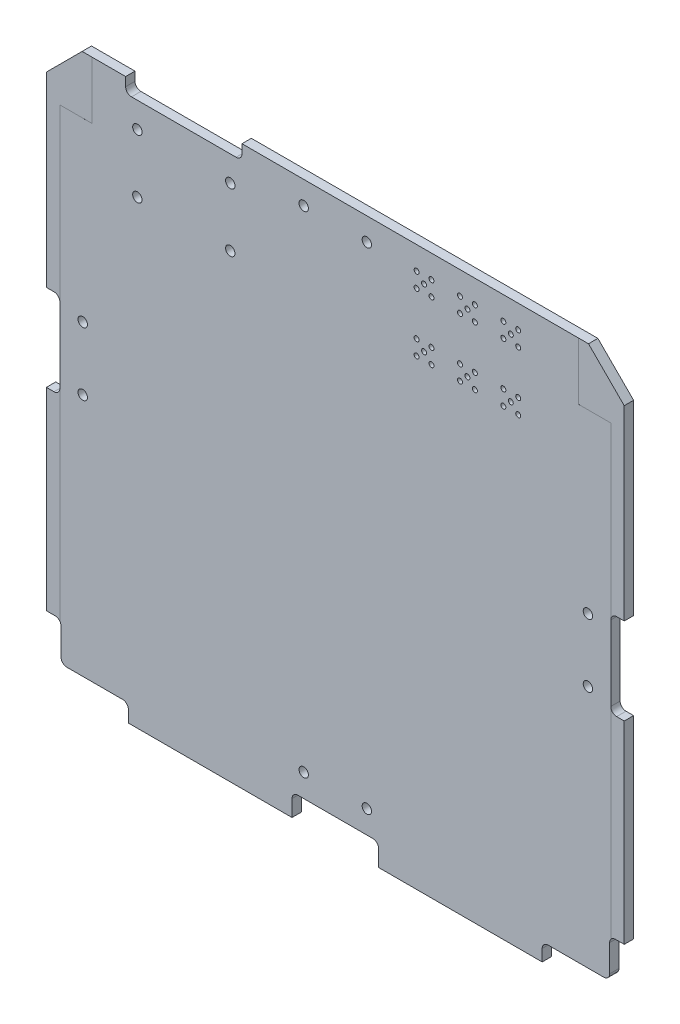
SolidWorks part; units mm, degrees
material "Oshpark board"
ref_plane "Front Plane" through (0, 0, 0) normal (0, 0, 1) x (1, 0, 0)
ref_plane "Top Plane" through (0, 0, 0) normal (0, 1, 0) x (1, 0, 0)
ref_plane "Right Plane" through (0, 0, 0) normal (1, 0, 0) x (0, 0, -1)
ref_plane "Plane4" through (0, 0, -0.0125) normal (0, 0, -1) x (-1, 0, 0)
sketch "Sketch1" plane through (0, 0, -0.0125) normal (0, 0, -1) x (-1, 0, 0)
  line L0 (35.3, -50) -> (35.3, -48)
  line L1 (36.3, -47) -> (45.8, -47)
  line L2 (46.8, -46) -> (46.8, -41.4)
  line L3 (47.8, -40.4) -> (49.3, -40.4)
  line L4 (49.3, -40.4) -> (49.3, 39.2)
  line L5 (49.3, 39.2) -> (43.2, 45.3)
  line L6 (43.2, 45.3) -> (35.5, 45.3)
  line L7 (35.5, 45.3) -> (35.5, 43.8) construction
  line L8 (34.5, 42.8) -> (4.5, 42.8) construction
  line L9 (3.5, 43.8) -> (3.5, 45.3) construction
  line L10 (3.5, 45.3) -> (-43.2, 45.3)
  line L11 (-43.2, 45.3) -> (-49.3, 39.2)
  line L12 (-49.3, 39.2) -> (-49.3, -40.4)
  line L13 (-49.3, -40.4) -> (-47.8, -40.4)
  line L14 (-46.8, -41.4) -> (-46.8, -46)
  line L15 (-45.8, -47) -> (-36.3, -47)
  line L16 (-35.3, -48) -> (-35.3, -50)
  line L17 (-35.3, -50) -> (35.3, -50)
  line L18 (0, -50) -> (0, 45.3) construction
  line L19 (19.5, 42.8) -> (19.5, 25.5258) construction
  line L20 (-13.87, 41.37) -> (-16.41, 38.83) construction
  line L21 (-21.27, 41.37) -> (-23.81, 38.83) construction
  line L22 (-28.67, 41.37) -> (-31.21, 38.83) construction
  line L23 (35.5, 45.3) -> (3.5, 45.3)
  arc A0 (35.3, -48) -> (36.3, -47) centre (36.3, -48) cw
  arc A1 (45.8, -47) -> (46.8, -46) centre (45.8, -46) ccw
  arc A2 (46.8, -41.4) -> (47.8, -40.4) centre (47.8, -41.4) cw
  arc A3 (35.5, 43.8) -> (34.5, 42.8) centre (34.5, 43.8) cw construction
  arc A4 (4.5, 42.8) -> (3.5, 43.8) centre (4.5, 43.8) cw construction
  arc A5 (-47.8, -40.4) -> (-46.8, -41.4) centre (-47.8, -41.4) cw
  arc A6 (-46.8, -46) -> (-45.8, -47) centre (-45.8, -46) ccw
  arc A7 (-36.3, -47) -> (-35.3, -48) centre (-36.3, -48) cw
  circle A8 centre (-21.27, 41.37) radius 0.425
  circle A9 centre (-23.81, 41.37) radius 0.425
  circle A10 centre (-22.54, 40.1) radius 0.425
  circle A11 centre (-13.87, 41.37) radius 0.425
  circle A12 centre (-23.81, 38.83) radius 0.425
  circle A13 centre (-16.41, 41.37) radius 0.425
  circle A14 centre (-15.14, 40.1) radius 0.425
  circle A15 centre (-21.27, 38.83) radius 0.425
  circle A16 centre (-28.67, 41.37) radius 0.425
  circle A17 centre (-31.21, 41.37) radius 0.425
  circle A18 centre (-16.41, 38.83) radius 0.425
  circle A19 centre (-29.94, 40.1) radius 0.425
  circle A20 centre (-31.21, 38.83) radius 0.425
  circle A21 centre (-28.67, 38.83) radius 0.425
  circle A22 centre (33.775, 38.54) radius 0.8 construction
  circle A23 centre (5.225, 38.54) radius 0.8 construction
  circle A24 centre (-13.87, 38.83) radius 0.425
  point P35 (-15.14, 40.1)
  dimension "D7" = 2.5
  dimension "D8" = 1.6
  dimension "D9" = 14.275
  dimension "D10" = 4.26
  dimension "D11" = 1
  dimension "D12" = 1
  dimension "D13" = 1
  dimension "D14" = 1
  dimension "D15" = 1
  dimension "D16" = 1
  dimension "D17" = 1
  dimension "D18" = 1
  dimension "D26" = 0.85
  dimension "D1" = 98.6
  dimension "D2" = 95.3
  dimension "D3" = 14
  dimension "D4" = 9.6
  dimension "D5" = 2.5
  dimension "D6" = 3
  dimension "D19" = 14
  dimension "D20" = 2.5
  dimension "D21" = 6.1
  dimension "D22" = 6.1
  dimension "D23" = 32
  dimension "D24" = 2.54
  dimension "D25" = 2.54
  dimension "D28" = 7.4
  dimension "D29" = 3.93
  dimension "D30" = 35.43
  dimension "D31" = 45
  dimension "D32" = 45
  dimension "D33" = 29.8
  dimension "D34" = 50
  dimension "D27" = 3
extrude "Boss-Extrude1" add sketch "Sketch1" against normal blind 1.6
sketch "thermalContacts_lower" plane through (0, 0, -0.0125) normal (0, 0, -1) x (-1, 0, 0)
  line L0 (47, 35.5) -> (47, -41.5) construction
  line L1 (41.5, 35.5) -> (41.5, 41.5) construction
  line L2 (41.5, 35.5) -> (47, 35.5) construction
  line L3 (47, 35.5) -> (47, -41.5)
  line L4 (41.5, 35.5) -> (41.5, 41.5)
  line L5 (41.5, 35.5) -> (47, 35.5)
  line L6 (-47, 35.5) -> (-47, -41.5) construction
  line L7 (-41.5, 35.5) -> (-47, 35.5) construction
  line L8 (-41.5, 35.5) -> (-41.5, 41.5) construction
  line L9 (-47, 35.5) -> (-47, -41.5)
  line L10 (-41.5, 35.5) -> (-47, 35.5)
  line L11 (-41.5, 35.5) -> (-41.5, 41.5)
  line L12 (-41.5, 41.5) -> (-41.5, 47) construction
  line L13 (-41.5, 41.5) -> (-49.5, 41.5) construction
  line L14 (-41.5, 41.5) -> (-41.5, 47)
  line L15 (-41.5, 41.5) -> (-49.5, 41.5) construction
  line L16 (41.5, 41.5) -> (41.5, 47) construction
  line L17 (41.5, 41.5) -> (49.5, 41.5) construction
  line L18 (41.5, 41.5) -> (41.5, 47)
  line L19 (41.5, 41.5) -> (49.5, 41.5) construction
  line L20 (47, -41.5) -> (59.8273, -41.5)
  line L21 (59.8273, -41.5) -> (59.8273, 47)
  line L22 (-56.1922, 47) -> (-41.5, 47)
  line L23 (41.5, 47) -> (59.8273, 47)
  line L24 (-56.1922, 47) -> (-56.1922, -41.5)
  line L25 (-47, -41.5) -> (-56.1922, -41.5)
sketch "thermalContacts_upper" plane through (0, 0, 1.5875) normal (0, 0, 1) x (1, 0, 0)
  line L3 (-47, 35.5) -> (-47, -41.5)
  line L4 (-41.5, 35.5) -> (-41.5, 41.5)
  line L5 (-41.5, 35.5) -> (-47, 35.5)
  line L9 (47, 35.5) -> (47, -41.5)
  line L10 (41.5, 35.5) -> (47, 35.5)
  line L11 (41.5, 35.5) -> (41.5, 41.5)
  line L14 (41.5, 41.5) -> (41.5, 47)
  line L15 (41.5, 41.5) -> (49.5, 41.5) construction
  line L18 (-41.5, 41.5) -> (-41.5, 47)
  line L19 (-41.5, 41.5) -> (-49.5, 41.5) construction
  line L20 (47, -41.5) -> (59.8273, -41.5)
  line L21 (59.8273, -41.5) -> (59.8273, 47)
  line L22 (59.8273, 47) -> (41.5, 47)
  line L23 (-41.5, 47) -> (-56.1922, 47)
  line L24 (-56.1922, 47) -> (-56.1922, -41.5)
  line L25 (-56.1922, -41.5) -> (-47, -41.5)
pattern_linear "LPattern2" count 2 spacing 10 along (0, -1, 0) of face at (14.295, 41.37, 1.5875) of face at (14.295, 38.83, 1.5875) of face at (15.565, 40.1, 1.5875) of face at (16.835, 38.83, 1.5875) of face at (21.695, 41.37, 1.5875) of face at (21.695, 38.83, 1.5875) of face at (22.965, 40.1, 1.5875) of face at (24.235, 38.83, 1.5875) of face at (24.235, 41.37, 1.5875) of face at (16.835, 41.37, 1.5875) of face at (29.095, 41.37, 1.5875) of face at (29.095, 38.83, 1.5875) of face at (30.365, 40.1, 1.5875) of face at (31.635, 38.83, 1.5875) of face at (31.635, 41.37, 1.5875)
extrude "slotFootprints_REF" cut sketch "thermalContacts_lower" against normal blind 0.0001
extrude "slotFootprints" cut sketch "thermalContacts_upper" against normal blind 0.0001
sketch "Sketch2" plane through (0, 0, 1.5875) normal (0, 0, 1) x (1, 0, 0)
  line L1 (-41.5, 45.3) -> (41.5, 45.3) construction
  line L2 (-49.3, -40.4) -> (-49.3, 39.2) construction
  line L3 (-35.775, 45.3) -> (-35.775, 43.8)
  line L4 (-41.5, 45.3) -> (41.5, 45.3) construction
  line L5 (-34.775, 42.8) -> (-16.925, 42.8)
  line L6 (-15.925, 43.8) -> (-15.925, 45.3)
  line L7 (-15.925, 45.3) -> (-35.775, 45.3)
  arc A1 (-16.925, 42.8) -> (-15.925, 43.8) centre (-16.925, 43.8) ccw
  arc A2 (-35.775, 43.8) -> (-34.775, 42.8) centre (-34.775, 43.8) ccw
  circle A3 centre (-33.775, 38.4723) radius 0.8
  circle A4 centre (-17.925, 38.4723) radius 0.8
  circle A5 centre (-17.925, 28.4723) radius 0.8
  circle A6 centre (-33.775, 28.4723) radius 0.8
  dimension "D2" = 1.6
  dimension "D5" = 1
  dimension "D1" = 15.85
  dimension "D3" = 6.8277
  dimension "D4" = 15.525
  dimension "D6" = 2
  dimension "D7" = 2
  dimension "D8" = 2.5
  dimension "D10" = 10
  dimension "D9" = 2
extrude "20pin_mounts" cut sketch "Sketch2" against normal through all
sketch "Sketch3" plane through (0, 0, -0.0125) normal (0, 0, -1) x (-1, 0, 0)
  line L0 (-49.3, -40.4) -> (-49.3, 39.2) construction
  line L1 (5.39, 41.4) -> (-5.38, 41.4) construction
  line L2 (43.1, -5.39) -> (43.1, 5.38) construction
  line L3 (15.925, 45.3) -> (-41.5, 45.3) construction
  line L4 (5.39, -42.3032) -> (-5.38, -42.3032) construction
  line L5 (-43.1, -5.39) -> (-43.1, 5.38) construction
  line L6 (41.5, 45.3) -> (35.775, 45.3) construction
  line L7 (43.1, -0.005) -> (-43.1, -0.005) construction
  line L8 (0.005, -42.3032) -> (0.005, 41.4) construction
  line L9 (49.3, -40.4) -> (49.3, 39.2) construction
  line L10 (-35.3, -50) -> (35.3, -50) construction
  line L11 (-43.1, -0.005) -> (-49.3, -0.005) construction
  line L12 (43.1, -0.005) -> (49.3, -0.005) construction
  line L13 (49.3, -40.4) -> (49.3, 39.2) construction
  line L14 (-49.3, 7.38) -> (-48, 7.38)
  line L15 (-47, 6.38) -> (-47, -6.39)
  line L16 (-48, -7.39) -> (-49.3, -7.39)
  line L17 (-49.3, -7.39) -> (-49.3, 7.38)
  line L18 (-49.3, -40.4) -> (-49.3, 39.2) construction
  line L19 (-47, 35.5) -> (-47, -40.8) construction
  line L20 (47, -40.8) -> (47, 35.5) construction
  line L21 (48, 7.38) -> (49.3, 7.38)
  line L22 (47, 6.38) -> (47, -6.39)
  line L23 (48, -7.39) -> (49.3, -7.39)
  line L24 (49.3, 7.38) -> (49.3, -7.39)
  line L26 (-6.38, -46.2032) -> (6.39, -46.2032)
  line L27 (-7.38, -47.2032) -> (-7.38, -50)
  line L28 (-7.38, -50) -> (7.39, -50)
  line L29 (7.39, -47.2032) -> (7.39, -50)
  arc A0 (-47, -6.39) -> (-48, -7.39) centre (-48, -6.39) cw
  arc A1 (-48, 7.38) -> (-47, 6.38) centre (-48, 6.38) cw
  circle A2 centre (5.39, 41.4) radius 0.8
  circle A3 centre (-5.38, 41.4) radius 0.8
  arc A4 (47, -6.39) -> (48, -7.39) centre (48, -6.39) ccw
  arc A5 (48, 7.38) -> (47, 6.38) centre (48, 6.38) ccw
  arc A6 (-6.38, -46.2032) -> (-7.38, -47.2032) centre (-6.38, -47.2032) ccw
  circle A7 centre (43.1, 5.38) radius 0.8
  circle A8 centre (43.1, -5.39) radius 0.8
  circle A9 centre (5.39, -42.3032) radius 0.8
  circle A10 centre (-5.38, -42.3032) radius 0.8
  circle A11 centre (-43.1, -5.39) radius 0.8
  circle A12 centre (-43.1, 5.38) radius 0.8
  arc A13 (6.39, -46.2032) -> (7.39, -47.2032) centre (6.39, -47.2032) cw
  point P16 (-47, -0.005)
  point P51 (47, -0.005)
  point P63 (0.005, -46.2032)
  dimension "D1" = 1.6
  dimension "D5" = 39.92
  dimension "D6" = 6.2
  dimension "D9" = 1
  dimension "D11" = 1
  dimension "D14" = 1
  dimension "D2" = 10.77
  dimension "D3" = 43.92
  dimension "D4" = 3.9
  dimension "D7" = 7.6968
  dimension "D8" = 2
  dimension "D10" = 2
  dimension "D12" = 3.9
  dimension "D13" = 2
extrude "12pin_mounts" cut sketch "Sketch3" against normal blind 10
